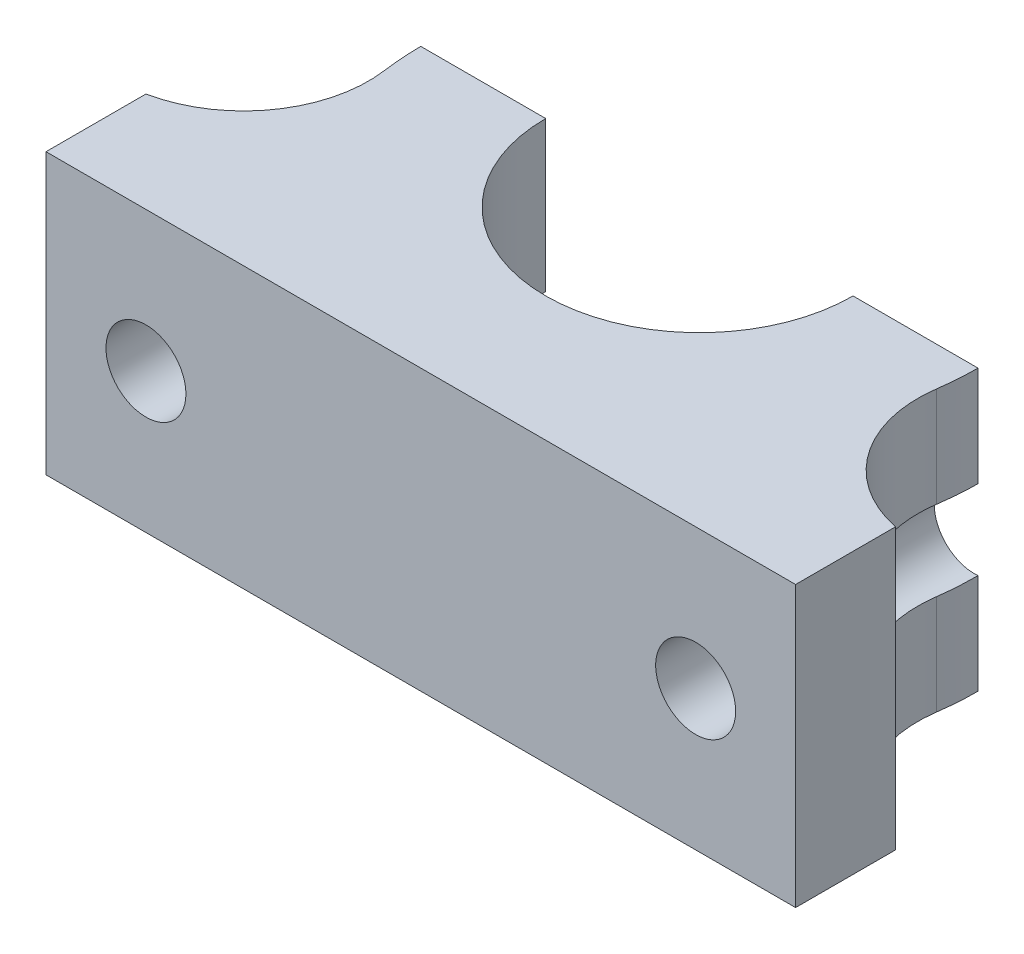
SolidWorks part; units mm, degrees
ref_plane "前视基准面" through (0, 0, 0) normal (0, 0, 1) x (1, 0, 0)
ref_plane "上视基准面" through (0, 0, 0) normal (0, 1, 0) x (1, 0, 0)
ref_plane "右视基准面" through (0, 0, 0) normal (1, 0, 0) x (0, 0, -1)
other "Configuration Table"
sketch "草图1" plane through (0, 0, 0) normal (0, 1, 0) x (1, 0, 0)
  line L0 (-11.15, 0) -> (-8.15, 0)
  line L1 (8.15, 0) -> (11.15, 0)
  arc A0 (-8.15, 0) -> (8.15, 0) centre (0, 0) ccw
  arc A1 (-11.15, 0) -> (11.15, 0) centre (0, 0) ccw
  circle A3 centre (0, 0) radius 11.15 construction
  circle A4 centre (0, 0) radius 8.15 construction
  point P4 (7.7939, 2.3828)
  point P7 (11.15, 0)
  dimension "D1" = 16.3
  dimension "D2" = 3
extrude "凸台-拉伸1" add sketch "草图1" along normal blind 5.2
sketch "草图2" plane through (0, 5.2, 0) normal (0, 1, 0) x (1, 0, 0)
  line L0 (-11.15, 0) -> (-6.15, 0)
  line L1 (6.15, 0) -> (11.15, 0)
  arc A0 (-11.15, 0) -> (11.15, 0) centre (0, 0) ccw
  arc A1 (-6.15, 0) -> (6.15, 0) centre (0, 0) ccw
  dimension "D1" = 12.3
extrude "凸台-拉伸2" add sketch "草图2" along normal blind 6
sketch "草图3" plane through (0, 11.2, 0) normal (0, 1, 0) x (1, 0, 0)
  line L0 (3.9115, -7.15) -> (15, -7.15)
  line L1 (-15, -7.15) -> (-3.9115, -7.15)
  line L2 (-15, -7.15) -> (-15, -11.15)
  line L3 (-15, -11.15) -> (15, -11.15)
  line L4 (15, -7.15) -> (15, -11.15)
  arc A0 (-11.15, 0) -> (11.15, 0) centre (0, 0) ccw construction
  arc A1 (-3.9115, -7.15) -> (3.9115, -7.15) centre (0, 0) ccw
  point P7 (0, -11.15)
  dimension "D1" = 11.15
  dimension "D2" = 30
  dimension "D3" = 0
  dimension "D4" = 4
extrude "凸台-拉伸3" add sketch "草图3" against normal up to surface (11.2 mm away) up to face at (0, 0, 4.825)
fillet "圆角1" radius 5 2 edges at (-8.5557, 5.6, 7.15) (8.5557, 5.6, 7.15)
sketch "草图4" plane through (0, 0, 11.15) normal (0, 0, 1) x (1, 0, 0)
  line L0 (-15, 0) -> (-15, 11.2) construction
  line L1 (15, 0) -> (15, 11.2) construction
  line L2 (-15, 11.2) -> (15, 11.2) construction
  circle A0 centre (-11, 5.6) radius 1.6
  circle A1 centre (11, 5.6) radius 1.6
  point P6 (-15, 5.6)
  point P9 (15, 5.6)
  point P12 (0, 11.2)
  dimension "D1" = 3.2
  dimension "D2" = 3.2
  dimension "D3" = 0
  dimension "D4" = 0
  dimension "D5" = 11
  dimension "D6" = 11
extrude "切除-拉伸1" cut sketch "草图4" against normal through all
equation "\"D1@草图3\"=22.3/2"
